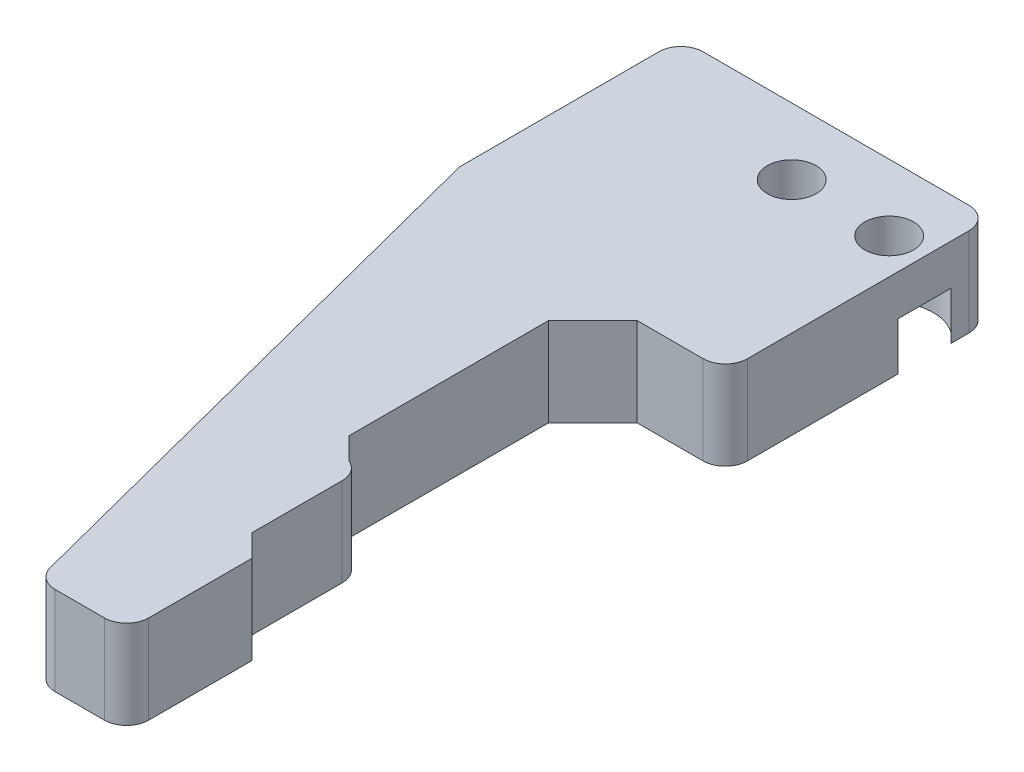
SolidWorks part; units mm, degrees
ref_plane "Front Plane" through (0, 0, 0) normal (0, 0, 1) x (1, 0, 0)
ref_plane "Top Plane" through (0, 0, 0) normal (0, 1, 0) x (1, 0, 0)
ref_plane "Right Plane" through (0, 0, 0) normal (1, 0, 0) x (0, 0, -1)
sketch "Sketch1" plane through (0, 0, 0) normal (0, 1, 0) x (1, 0, 0)
  line L0 (-100, 0) -> (100, 0) construction
  line L1 (0, -100) -> (0, 100) construction
  line L3 (8.5, 4.9075) -> (8.5, 14.7224) construction
  line L4 (8.5, 14.7224) -> (0, 19.6299) construction
  line L5 (0, 19.6299) -> (-8.5, 14.7224) construction
  line L6 (-8.5, 14.7224) -> (-8.5, 4.9075) construction
  line L7 (-8.5, 4.9075) -> (0, 0) construction
  line L8 (0, 0) -> (8.5, 4.9075) construction
  line L9 (11, 17.4641) -> (11, 30.1658) construction
  line L10 (11, 30.1658) -> (0, 36.5167) construction
  line L11 (0, 36.5167) -> (-11, 30.1658) construction
  line L12 (-11, 30.1658) -> (-11, 17.4641) construction
  line L13 (-11, 17.4641) -> (0, 11.1132) construction
  line L14 (0, 11.1132) -> (11, 17.4641) construction
  line L15 (15, 50.4752) -> (0, 59.1355) construction
  line L16 (0, 59.1355) -> (-15, 50.4752) construction
  line L17 (-15, 50.4752) -> (-15, 33.1547) construction
  line L18 (-15, 33.1547) -> (0, 24.4944) construction
  line L19 (0, 24.4944) -> (15, 33.1547) construction
  line L20 (15, 33.1547) -> (15, 50.4752) construction
  circle A0 centre (0, 9.815) radius 8.5 construction
  circle A1 centre (0, 23.815) radius 11 construction
  circle A2 centre (0, 41.815) radius 15 construction
  point P4 (0, 0)
  point P8 (0, 0)
  dimension "D2" = 17
  dimension "D4" = 22
  dimension "D6" = 30
  dimension "D1" = 200
  dimension "D3" = 14
  dimension "D5" = 18
sketch "Sketch2" plane through (0, 0, 0) normal (0, 1, 0) x (1, 0, 0)
  line L0 (0, 59.1355) -> (-14.95, 59.1355)
  line L1 (-14.95, 59.1355) -> (-14.95, 29.1355)
  line L2 (-14.95, 29.1355) -> (-10.95, 29.1355)
  line L3 (-10.95, 29.1355) -> (-10.95, 14.1355)
  line L4 (-10.95, 14.1355) -> (-8.45, 14.1355)
  line L5 (-8.45, 14.1355) -> (-8.45, 0)
  line L6 (-100, 0) -> (100, 0) construction
  line L7 (0, -100) -> (0, 100) construction
  line L8 (0, 59.1355) -> (0, 89.1355)
  line L9 (0, 89.1355) -> (-35, 89.1355)
  line L12 (-8.45, 0) -> (-18.45, 0)
  line L13 (-18.45, 0) -> (-35, 64.1355)
  line L14 (-35, 64.1355) -> (-35, 89.1355)
  dimension "D1" = 14.95
  dimension "D2" = 4
  dimension "D3" = 8.45
  dimension "D4" = 30
  dimension "D5" = 15
  dimension "D6" = 30
  dimension "D7" = 10
  dimension "D8" = 25
  dimension "D9" = 35
extrude "Boss-Extrude1" add sketch "Sketch2" along normal blind 10
chamfer "Chamfer1" distance 5 angle 45 1 edges at (-14.95, 5, -59.1355)
chamfer "Chamfer2" distance 2.5 angle 45 2 edges at (-10.95, 5, -14.1355) (-14.95, 5, -29.1355)
fillet "Fillet1" radius 2.5 6 edges at (0, 5, -89.1355) (-8.45, 5, 0) (-18.45, 5, 0) (-35, 5, -89.1355) (0, 5, -59.1355) (-10.95, 5, -29.1355)
sketch "Sketch3" plane through (0, 10, 0) normal (0, 1, 0) x (1, 0, 0)
  line L0 (-15, 81.6355) -> (-4, 81.6355) construction
  line L1 (-2.5, 89.1355) -> (-32.5, 89.1355) construction
  line L2 (0, -100) -> (0, 100) construction
  dimension "D1" = 11
  dimension "D2" = 7.5
  dimension "D3" = 4
hole_wizard "CBORE for M5 Hex Socket Head Cap Screw5" positions "Sketch10" profile "Sketch11" counterbore size "M5" standard "DIN"
sketch "Sketch10" plane through (0, 0, 0) normal (0, -1, 0) x (-1, 0, 0)
  point P0 (4, 81.6355)
  point P3 (15, 81.6355)
sketch "Sketch11" plane through (-4, 0, -81.6355) normal (1, 0, 0) x (0, 0, -1)
  line L0 (0, 0) -> (0, 11.6524)
  line L1 (0, 11.6524) -> (2.75, 10)
  line L2 (2.75, 10) -> (2.75, 5.4)
  line L3 (2.75, 5.4) -> (5, 5.4)
  line L4 (5, 5.4) -> (5, 0)
  line L5 (5, 0) -> (0, 0)
  line L10 (0, 11.6524) -> (-2.75, 10) construction
  line L11 (0, -6.35) -> (0, 107.95) construction
  dimension "Hole Dia." = 5.5
  dimension "Hole Depth" = 10
  dimension "C'Bore Dia." = 10
  dimension "C'Bore Depth" = 5.4
  dimension "Drill Angle" = 118
